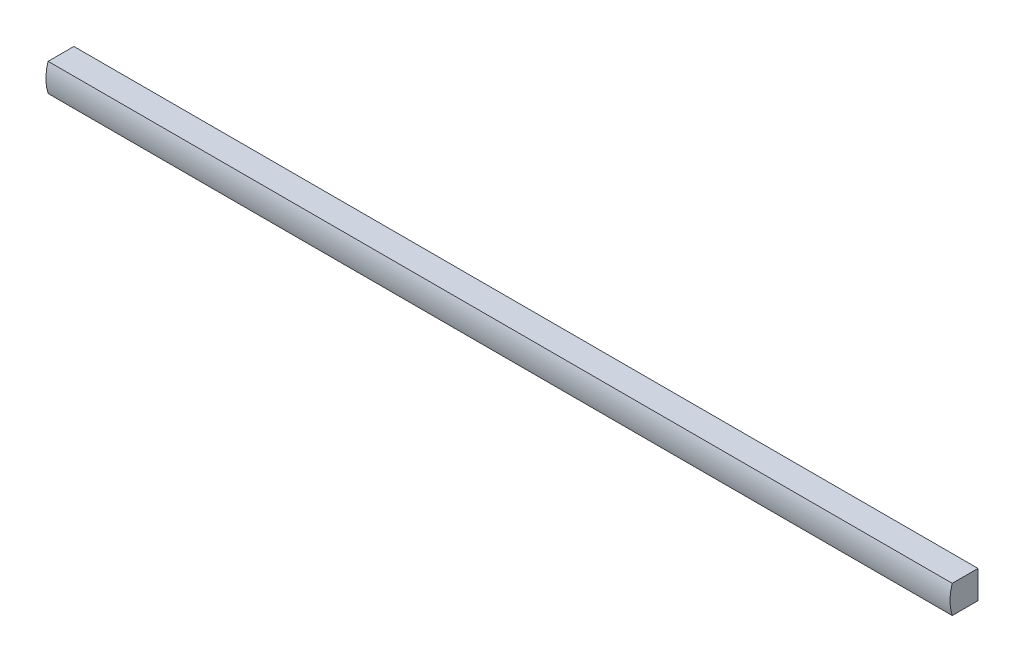
SolidWorks part; units mm, degrees
ref_plane "Front Plane" through (0, 0, 0) normal (0, 0, 1) x (1, 0, 0)
ref_plane "Top Plane" through (0, 0, 0) normal (0, 1, 0) x (1, 0, 0)
ref_plane "Right Plane" through (0, 0, 0) normal (1, 0, 0) x (0, 0, -1)
sketch "Sketch1" plane through (0, 0, 0) normal (1, 0, 0) x (0, 0, -1)
  line L1 (0, 0) -> (9.525, 0)
  line L2 (0, 0) -> (0, 9.525)
  line L3 (0, 9.525) -> (9.525, 9.525)
  line L4 (9.525, 0) -> (9.525, 9.525)
  arc A0 (0.7556, 0) -> (0.7426, 9.525) centre (15.5137, 4.7827) cw
  dimension "D2" = 8.7824
  dimension "D1" = 9.525
  dimension "D3" = 8.7694
extrude "Boss-Extrude1" add sketch "Sketch1" against normal blind 307.975 contours L1 L4 L3 L2 region at (0, 4.7636, -4.8835)
